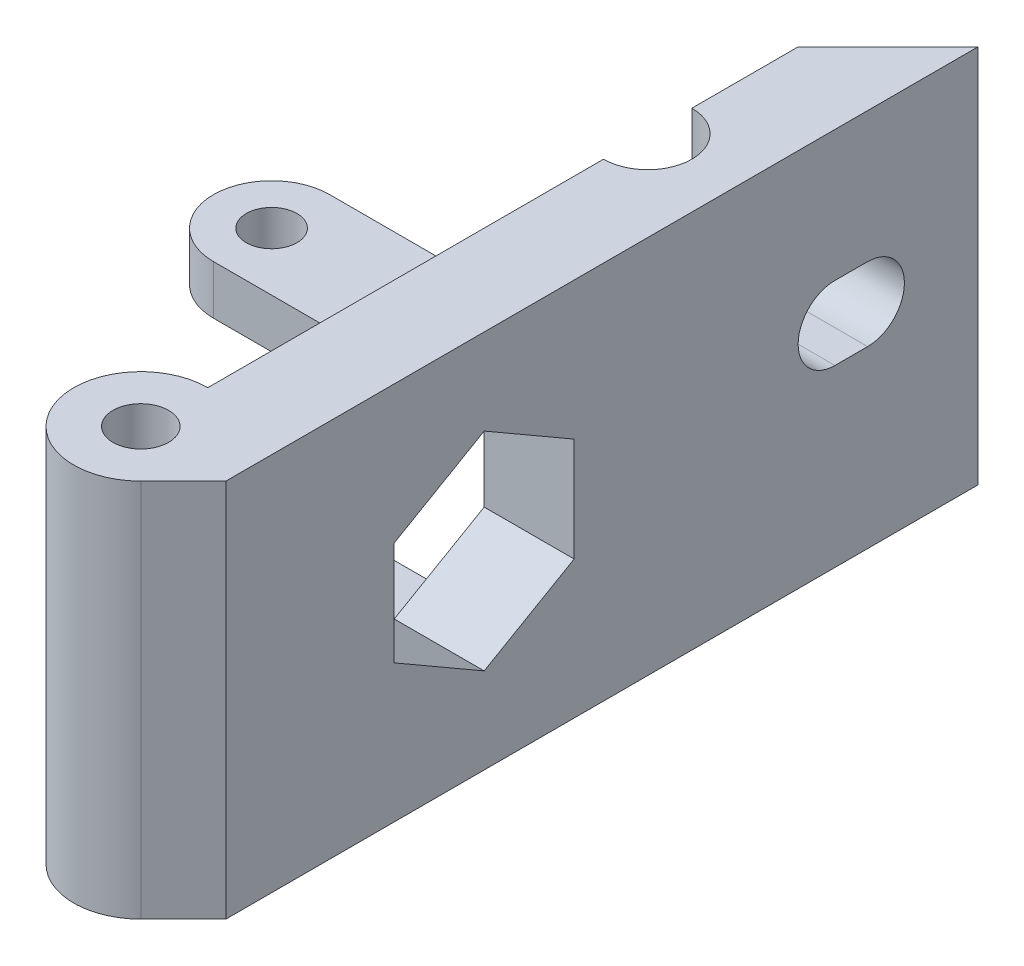
SolidWorks part; units mm, degrees
material "6061-T6 (SS)"
ref_plane "Front Plane" through (0, 0, 0) normal (0, 0, 1) x (1, 0, 0)
ref_plane "Top Plane" through (0, 0, 0) normal (0, 1, 0) x (1, 0, 0)
ref_plane "Right Plane" through (0, 0, 0) normal (1, 0, 0) x (0, 0, -1)
ref_axis "Axis1" through (0, 0, 55) along (0, 0, -1)
sketch "outline" plane through (0, 0, 0) normal (0, 1, 0) x (1, 0, 0)
  line L1 (-25, -100) -> (125, -100)
  line L2 (-25, -100) -> (-25, 100)
  line L3 (-25, 100) -> (125, 100)
  line L4 (125, -100) -> (125, 100)
  line L5 (-25, -100) -> (125, 100) construction
  line L6 (-25, 100) -> (125, -100) construction
  line L7 (125, 100) -> (275, 100)
  line L8 (125, 100) -> (125, -100)
  line L9 (125, -100) -> (275, -100)
  line L10 (275, 100) -> (275, -100)
  line L11 (125, 100) -> (275, -100) construction
  line L12 (125, -100) -> (275, 100) construction
  point P4 (50, 0)
  point P11 (200, 0)
  dimension "D1" = 150
  dimension "D2" = 200
  dimension "D3" = 150
  dimension "D4" = 50
sketch "x_carriage_plate" plane through (0, 0, 0) normal (0, 1, 0) x (1, 0, 0)
  line L0 (20, -4.5) -> (20, 0) construction
  line L1 (0, 0) -> (64, 0) construction
  line L2 (0, 0) -> (0, 37.5) construction
  line L3 (10, 47.5) -> (54, 47.5) construction
  line L4 (64, 0) -> (64, 37.5) construction
  line L5 (0, 0) -> (64, 47.5) construction
  line L6 (0, 47.5) -> (64, 0) construction
  line L7 (44, -4.5) -> (44, 0) construction
  circle A0 centre (13, 14.25) radius 1.5
  circle A1 centre (30.5, 30.15) radius 1.5
  circle A2 centre (12, 35.6) radius 2.5
  circle A3 centre (52, 35.6) radius 2.5
  arc A4 (64, 37.5) -> (54, 47.5) centre (54, 37.5) ccw construction
  arc A5 (10, 47.5) -> (0, 37.5) centre (10, 37.5) ccw construction
  circle A6 centre (55.5, 23.05) radius 1.5
  circle A7 centre (41.5, 23.05) radius 1.5
  arc A8 (20, -4.5) -> (44, -4.5) centre (32, -4.5) ccw construction
  circle A9 centre (32, -4.6) radius 3.6
  point P4 (32, 23.75)
  dimension "D7" = 5
  dimension "D11" = 3
  dimension "D12" = 10
  dimension "D16" = 24
  dimension "D19" = 7.2
  dimension "D1" = 64
  dimension "D2" = 47.5
  dimension "D3" = 13
  dimension "D4" = 12
  dimension "D5" = 30.5
  dimension "D6" = 40
  dimension "D8" = 11.9
  dimension "D9" = 14.25
  dimension "D10" = 30.15
  dimension "D13" = 8.5
  dimension "D14" = 22.5
  dimension "D15" = 24.45
  dimension "D17" = 4.5
  dimension "D18" = 32
  dimension "D20" = 4.6
sketch "front_profile" plane through (0, 0, 0) normal (0, 1, 0) x (1, 0, 0)
  line L0 (0, 0) -> (64, 0) construction
  line L1 (37.35, 43.55) -> (59.65, 43.55)
  line L2 (37.35, 43.55) -> (37.35, -18.75)
  line L3 (37.35, -18.75) -> (59.65, -18.75)
  line L4 (59.65, 43.55) -> (59.65, -18.75)
  line L5 (37.35, 43.55) -> (59.65, -18.75) construction
  line L6 (37.35, -18.75) -> (59.65, 43.55) construction
  line L7 (48.5, 12.4) -> (48.5, 23.05) construction
  line L8 (48.5, 23.05) -> (41.5, 23.05) construction
  line L9 (48.5, 23.05) -> (55.5, 23.05) construction
  line L10 (48.5, 12.4) -> (23.5, 12.4) construction
  line L15 (64, 0) -> (64, 37.5) construction
  line L16 (69.5, -6.2877) -> (69.5, -3.1123)
  line L21 (69.5, -3.1123) -> (66.75, -1.5246)
  line L22 (66.75, -1.5246) -> (64, -3.1123)
  line L23 (43.5, 44.75) -> (53.5, 44.75)
  line L24 (43.5, 44.75) -> (43.5, 43.55)
  line L25 (43.5, 43.55) -> (53.5, 43.55)
  line L26 (53.5, 44.75) -> (53.5, 43.55)
  line L27 (43.5, 44.75) -> (53.5, 43.55) construction
  line L28 (43.5, 43.55) -> (53.5, 44.75) construction
  line L30 (23.5, 90.5) -> (65.5, 90.5)
  line L31 (23.5, 90.5) -> (23.5, 48.5)
  line L32 (23.5, 48.5) -> (65.5, 48.5)
  line L33 (65.5, 90.5) -> (65.5, 48.5)
  line L34 (23.5, 90.5) -> (65.5, 48.5) construction
  line L35 (23.5, 48.5) -> (65.5, 90.5) construction
  line L36 (10, 47.5) -> (54, 47.5) construction
  line L37 (29, 85) -> (60, 85) construction
  line L38 (29, 85) -> (29, 54) construction
  line L39 (29, 54) -> (60, 54) construction
  line L40 (60, 85) -> (60, 54) construction
  line L41 (29, 85) -> (60, 54) construction
  line L42 (29, 54) -> (60, 85) construction
  line L43 (64, -3.1123) -> (64, -6.2877)
  line L44 (64, -6.2877) -> (66.75, -7.8754)
  line L45 (66.75, -7.8754) -> (69.5, -6.2877)
  circle A0 centre (29, 54) radius 1.5
  circle A1 centre (60, 54) radius 1.5
  circle A2 centre (60, 85) radius 1.5
  circle A3 centre (29, 85) radius 1.5
  circle A4 centre (44.5, 69.5) radius 2.5
  circle A6 centre (66.75, -4.7) radius 2.75 construction
  circle A7 centre (66.75, -4.7) radius 1.7 construction
  circle A8 centre (66.75, -4.7) radius 4.7
  circle A9 centre (52.5, 69.5) radius 2.5
  arc A10 (52.5, 69.5) -> (77.2192, 54) centre (60, 54) cw construction
  circle A14 centre (60, 54) radius 1.7 construction
  circle A15 centre (60, 54) radius 4.2 construction
  arc A16 (48.8726, 0) -> (62.8779, -7.3641) centre (48.8726, -17) cw
  arc A17 (69.8364, -1.1554) -> (64, 11.6654) centre (81, 11.6654) cw
  point P0 (48.5, 12.4)
  point P15 (48.5, 44.15)
  point P30 (44.5, 69.5)
  point P37 (44.5, 69.5)
  dimension "D12" = 3
  dimension "D13" = 5
  dimension "D4" = 5.5
  dimension "D5" = 3.4
  dimension "D16" = 3.4
  dimension "D18" = 17
  dimension "D1" = 62.3
  dimension "D2" = 22.3
  dimension "D3" = 18.75
  dimension "D8" = 1.2
  dimension "D9" = 10
  dimension "D10" = 42
  dimension "D11" = 31
  dimension "D7" = 4
  dimension "D14" = 8
  dimension "D15" = 25
  dimension "D19" = 1
  dimension "D6" = 3
  dimension "D17" = 2.5
sketch "idler_door" plane through (0, 0, 0) normal (0, 1, 0) x (1, 0, 0)
  line L0 (60, 85) -> (60, 54) construction
  line L1 (65.5, 90.5) -> (65.5, 48.5) construction
  line L2 (23.5, 48.5) -> (65.5, 90.5) construction
  line L3 (60, 87.7) -> (60, 88.7) construction
  line L4 (60, 58.1) -> (60, 82.3) construction
  line L5 (62.8991, 51.1009) -> (65.5, 53.7017) construction
  line L6 (65.5, 99.7) -> (65.5, 53.7017) construction
  line L7 (52.5, 65.95) -> (60, 65.95) construction
  line L8 (52.5, 73.05) -> (60, 73.05) construction
  line L9 (50.5, 93.2) -> (80.5, 93.2)
  line L10 (50.5, 93.2) -> (50.5, 88.7)
  line L11 (50.5, 88.7) -> (80.5, 88.7)
  line L12 (80.5, 93.2) -> (80.5, 88.7)
  line L13 (50.5, 93.2) -> (80.5, 88.7) construction
  line L14 (50.5, 88.7) -> (80.5, 93.2) construction
  line L15 (80.5, 94.45) -> (84.5, 94.45)
  line L16 (80.5, 94.45) -> (80.5, 87.45)
  line L17 (80.5, 87.45) -> (84.5, 87.45)
  line L18 (84.5, 94.45) -> (84.5, 87.45)
  line L19 (80.5, 94.45) -> (84.5, 87.45) construction
  line L20 (80.5, 87.45) -> (84.5, 94.45) construction
  line L21 (60, 94.2) -> (65.5, 99.7) construction
  line L22 (60, 88.7) -> (60, 93.2) construction
  line L23 (60, 93.2) -> (60, 94.2) construction
  line L25 (53, 94.45) -> (56, 94.45)
  line L26 (53, 94.45) -> (53, 87.45)
  line L27 (53, 87.45) -> (56, 87.45)
  line L28 (56, 94.45) -> (56, 87.45)
  line L29 (53, 94.45) -> (56, 87.45) construction
  line L30 (53, 87.45) -> (56, 94.45) construction
  circle A2 centre (52.5, 69.5) radius 1.55
  circle A5 centre (52.5, 69.5) radius 3.55
  circle A8 centre (60, 85) radius 1.7 construction
  circle A9 centre (60, 85) radius 2.7 construction
  circle A11 centre (60, 54) radius 1.7 construction
  circle A12 centre (60, 54) radius 1.7
  circle A14 centre (60, 54) radius 4.1
  point P8 (65.5, 90.95)
  point P36 (82.5, 90.95)
  point P43 (54.5, 90.95)
  dimension "D1" = 2.4
  dimension "D4" = 4.5
  dimension "D5" = 3.1
  dimension "D8" = 5.5
  dimension "D9" = 4
  dimension "D11" = 3.4
  dimension "D16" = 4
  dimension "D3" = 15
  dimension "D7" = 7
  dimension "D2" = 45
  dimension "D10" = 30
  dimension "D13" = 1
  dimension "D14" = 3
  dimension "D15" = 7
  dimension "D6" = 2
  dimension "D12" = 1
sketch "side_profile" plane through (0, 0, 0) normal (0, 1, 0) x (1, 0, 0)
  line L0 (125, 100) -> (275, 100) construction
  line L1 (255, 100) -> (275, 100)
  line L2 (255, 100) -> (255, -100)
  line L3 (255, -100) -> (275, -100)
  line L4 (275, 100) -> (275, -100)
  line L5 (255, 100) -> (275, -100) construction
  line L6 (255, -100) -> (275, 100) construction
  line L7 (201.8, 100) -> (201.8, -100) construction
  line L8 (228.15, -10) -> (248.15, -10)
  line L9 (228.15, -10) -> (228.15, -30)
  line L10 (228.15, -30) -> (248.15, -30)
  line L11 (248.15, -10) -> (248.15, -30)
  line L12 (228.15, -10) -> (248.15, -30) construction
  line L13 (228.15, -30) -> (248.15, -10) construction
  line L14 (221.8, 12) -> (224.3, 12)
  line L15 (221.8, 12) -> (221.8, -35.5)
  line L16 (221.8, -35.5) -> (224.3, -35.5)
  line L17 (224.3, 12) -> (224.3, -35.5)
  line L18 (221.8, 12) -> (224.3, -35.5) construction
  line L19 (221.8, -35.5) -> (224.3, 12) construction
  line L20 (209.7, 55) -> (249.7, 55)
  line L21 (209.7, 55) -> (209.7, 13)
  line L22 (209.7, 13) -> (249.7, 13)
  line L23 (249.7, 55) -> (249.7, 13)
  line L24 (209.7, 55) -> (249.7, 13) construction
  line L25 (209.7, 13) -> (249.7, 55) construction
  line L26 (185.7, 36.5) -> (209.7, 36.5)
  line L27 (185.7, 36.5) -> (185.7, 31.5)
  line L28 (185.7, 31.5) -> (209.7, 31.5)
  line L29 (209.7, 36.5) -> (209.7, 31.5)
  line L30 (185.7, 36.5) -> (209.7, 31.5) construction
  line L31 (185.7, 31.5) -> (209.7, 36.5) construction
  line L32 (207.7, 23) -> (209.7, 23)
  line L33 (207.7, 23) -> (207.7, 45)
  line L34 (207.7, 45) -> (209.7, 45)
  line L35 (209.7, 23) -> (209.7, 45)
  line L36 (207.7, 23) -> (209.7, 45) construction
  line L37 (207.7, 45) -> (209.7, 23) construction
  line L38 (125, -100) -> (275, -100) construction
  line L39 (186.3, -35.5) -> (186.3, 55)
  line L40 (187.7, 34.9851) -> (207.7, 34.9851) construction
  line L41 (221.8, -35.5) -> (224.3, -35.5)
  line L42 (221.8, -35.5) -> (221.8, -52)
  line L43 (221.8, -52) -> (224.3, -52)
  line L44 (224.3, -35.5) -> (224.3, -52)
  line L45 (221.8, -35.5) -> (224.3, -52) construction
  line L46 (221.8, -52) -> (224.3, -35.5) construction
  line L47 (190.7, 34) -> (204.7, 34) construction
  line L48 (197.7, 34) -> (197.7, 34.9851) construction
  line L49 (249.7, 34) -> (209.7, 34) construction
  line L50 (199.8, 28) -> (203.8, 28)
  line L51 (199.8, 28) -> (199.8, -35.0215)
  line L52 (199.8, -35.0215) -> (203.8, -35.0215)
  line L53 (203.8, 28) -> (203.8, -35.0215)
  line L54 (199.8, 28) -> (203.8, -35.0215) construction
  line L55 (199.8, -35.0215) -> (203.8, 28) construction
  line L56 (214.7, 18.5) -> (186.3, 18.5) construction
  line L57 (214.7, 49.5) -> (214.7, 18.5) construction
  line L58 (186.3, 20.2) -> (214.7, 20.2)
  line L59 (186.3, 20.2) -> (186.3, 16.8)
  line L60 (186.3, 16.8) -> (214.7, 16.8)
  line L61 (214.7, 20.2) -> (214.7, 16.8)
  line L62 (186.3, 20.2) -> (214.7, 16.8) construction
  line L63 (186.3, 16.8) -> (214.7, 20.2) construction
  line L64 (186.3, 55) -> (183.3, 55)
  line L69 (183.3, 55) -> (183.3, -35.5)
  line L70 (183.3, -35.5) -> (186.3, -35.5)
  line L71 (186.3, 49.5) -> (214.7, 49.5) construction
  line L72 (190.7, 38.5) -> (204.7, 38.5)
  line L73 (190.7, 38.5) -> (190.7, 29.5)
  line L74 (190.7, 29.5) -> (204.7, 29.5)
  line L75 (204.7, 38.5) -> (204.7, 29.5)
  line L76 (190.7, 38.5) -> (204.7, 29.5) construction
  line L77 (190.7, 29.5) -> (204.7, 38.5) construction
  line L78 (186.3, 51.2) -> (214.7, 51.2)
  line L79 (186.3, 51.2) -> (186.3, 47.8)
  line L80 (186.3, 47.8) -> (214.7, 47.8)
  line L81 (214.7, 51.2) -> (214.7, 47.8)
  line L82 (186.3, 51.2) -> (214.7, 47.8) construction
  line L83 (186.3, 47.8) -> (214.7, 51.2) construction
  line L84 (185.3, 52.2) -> (215.7, 52.2) construction
  line L85 (215.7, 52.2) -> (215.7, 46.8) construction
  line L86 (185.3, 46.8) -> (215.7, 46.8) construction
  line L87 (185.3, 52.2) -> (185.3, 46.8) construction
  circle A3 centre (196.55, 55.45) radius 2.25
  circle A4 centre (196.55, 55.45) radius 3.25 construction
  point P4 (265, 0)
  point P8 (238.15, -20)
  point P13 (197.7, 34)
  point P16 (223.05, -11.75)
  point P22 (229.7, 34)
  point P35 (208.7, 34)
  point P39 (223.05, -43.75)
  point P42 (201.8, -3.5107)
  point P49 (197.7, 34.9851)
  point P54 (200.5, 49.5)
  point P68 (214.7, 34)
  dimension "D13" = 5
  dimension "D10" = 42
  dimension "D25" = 4.5
  dimension "D1" = 20
  dimension "D2" = 20
  dimension "D3" = 6.85
  dimension "D4" = 20
  dimension "D5" = 2.5
  dimension "D6" = 3.85
  dimension "D7" = 47.5
  dimension "D8" = 22
  dimension "D9" = 40
  dimension "D11" = 24
  dimension "D12" = 5.3
  dimension "D14" = 2
  dimension "D15" = 22
  dimension "D16" = 5.9
  dimension "D17" = 20
  dimension "D18" = 12.1
  dimension "D19" = 16.5
  dimension "D20" = 35.5
  dimension "D21" = 20
  dimension "D22" = 14
  dimension "D23" = 2.9
  dimension "D26" = 23.4
  dimension "D27" = 15.5
  dimension "D28" = 4
  dimension "D32" = 3.4
  dimension "D31" = 5
  dimension "D33" = 31
  dimension "D34" = 6
  dimension "D35" = 3
  dimension "D24" = 9
  dimension "D36" = 1
  dimension "D29" = 1
  dimension "D30" = 1
sketch "Sketch1" plane through (0, 0, 0) normal (0, 1, 0) x (1, 0, 0)
  line L0 (60, 94.2) -> (65.5, 99.7) construction
  line L1 (60, 93.2) -> (60, 94.2) construction
  line L2 (60, 88.7) -> (60, 93.2) construction
  line L3 (60, 87.7) -> (60, 88.7) construction
  line L4 (65.5, 99.7) -> (65.5, 53.7017) construction
  line L5 (60, 58.1) -> (60, 82.3) construction
  line L6 (62.8991, 51.1009) -> (65.5, 53.7017) construction
  line L7 (60, 94.2) -> (65.5, 99.7)
  line L8 (60, 93.2) -> (60, 94.2)
  line L9 (60, 88.7) -> (60, 93.2)
  line L10 (60, 87.7) -> (60, 88.7)
  line L11 (65.5, 99.7) -> (65.5, 53.7017)
  line L12 (60, 58.1) -> (60, 82.3)
  line L13 (62.8991, 51.1009) -> (65.5, 53.7017)
  circle A0 centre (60, 54) radius 1.7 construction
  circle A1 centre (60, 54) radius 4.1 construction
  circle A2 centre (60, 54) radius 1.7
  arc A3 (60, 58.1) -> (62.8991, 51.1009) centre (60, 54) ccw
  circle A4 centre (60, 85) radius 2.7 construction
  arc A5 (60, 82.3) -> (60, 87.7) centre (60, 85) ccw
  arc A6 (60, 87.7) -> (60, 82.3) centre (60, 85) ccw construction
  arc A7 (62.8991, 51.1009) -> (60, 58.1) centre (60, 54) ccw construction
extrude "Boss-Extrude1" add sketch "Sketch1" along normal mid plane 23.2
sketch "Sketch2" plane through (65.5, 0, 0) normal (1, 0, 0) x (0, 0, -1)
  line L0 (53.7017, 11.6) -> (99.7, 11.6) construction
  line L1 (90.95, 1.35) -> (92.95, 1.35) construction
  line L2 (90.95, 3.6) -> (92.95, 3.6)
  line L3 (90.95, -0.9) -> (92.95, -0.9)
  circle A0 centre (90.95, 1.35) radius 2.25 construction
  arc A1 (90.95, 3.6) -> (90.95, -0.9) centre (90.95, 1.35) ccw
  arc A2 (92.95, -0.9) -> (92.95, 3.6) centre (92.95, 1.35) ccw
  point P4 (91.95, 1.35)
  dimension "D2" = 4.5
  dimension "D1" = 10.25
  dimension "D3" = 2
extrude "Cut-Extrude1" cut sketch "Sketch2" against normal through all
sketch "Sketch3" plane through (0, -11.6, 0) normal (0, -1, 0) x (1, 0, 0)
  line L0 (52.5, -65.95) -> (60, -65.95) construction
  line L1 (52.5, -73.05) -> (60, -73.05) construction
  line L2 (52.5, -65.95) -> (60, -65.95)
  line L3 (52.5, -73.05) -> (60, -73.05)
  line L4 (60, -65.95) -> (60, -73.05)
  circle A0 centre (52.5, -69.5) radius 1.55 construction
  circle A1 centre (52.5, -69.5) radius 3.55 construction
  circle A2 centre (52.5, -69.5) radius 1.55
  arc A3 (52.5, -65.95) -> (52.5, -73.05) centre (52.5, -69.5) ccw
  arc A4 (52.5, -73.05) -> (52.5, -65.95) centre (52.5, -69.5) ccw construction
extrude "Boss-Extrude2" add sketch "Sketch3" against normal blind 3 from offset 1.8 offset against normal yes
extrude "Boss-Extrude3" add sketch "Sketch3<2>" against normal blind 3 from offset 19.2 offset against normal yes
sketch "Sketch3<2>" plane through (0, -11.6, 0) normal (0, -1, 0) x (1, 0, 0) same geometry as "Sketch3"
sketch "Sketch4" plane through (65.5, 0, 0) normal (1, 0, 0) x (0, 0, -1)
  line L0 (69.5, -11.6) -> (69.5, 11.6) construction
  line L1 (65.95, -11.6) -> (73.05, -11.6) construction
  line L2 (53.7017, 11.6) -> (99.7, 11.6) construction
  line L4 (75, -3.1754) -> (75, 3.1754)
  line L5 (75, 3.1754) -> (69.5, 6.3509)
  line L6 (69.5, 6.3509) -> (64, 3.1754)
  line L7 (64, 3.1754) -> (64, -3.1754)
  line L8 (64, -3.1754) -> (69.5, -6.3509)
  line L9 (69.5, -6.3509) -> (75, -3.1754)
  circle A0 centre (69.5, 0) radius 5.5 construction
  dimension "12" = 11
extrude "Cut-Extrude2" cut sketch "Sketch4" against normal up to surface (5.5 mm away) up to face at (60, -8.3, -69.5)
equation "\"D1@front_profile\" = 62.300mm"
equation "\"D19@side_profile\" = 4.5 + 12"
equation "\"D16@side_profile\"=2.900mm + 3"
